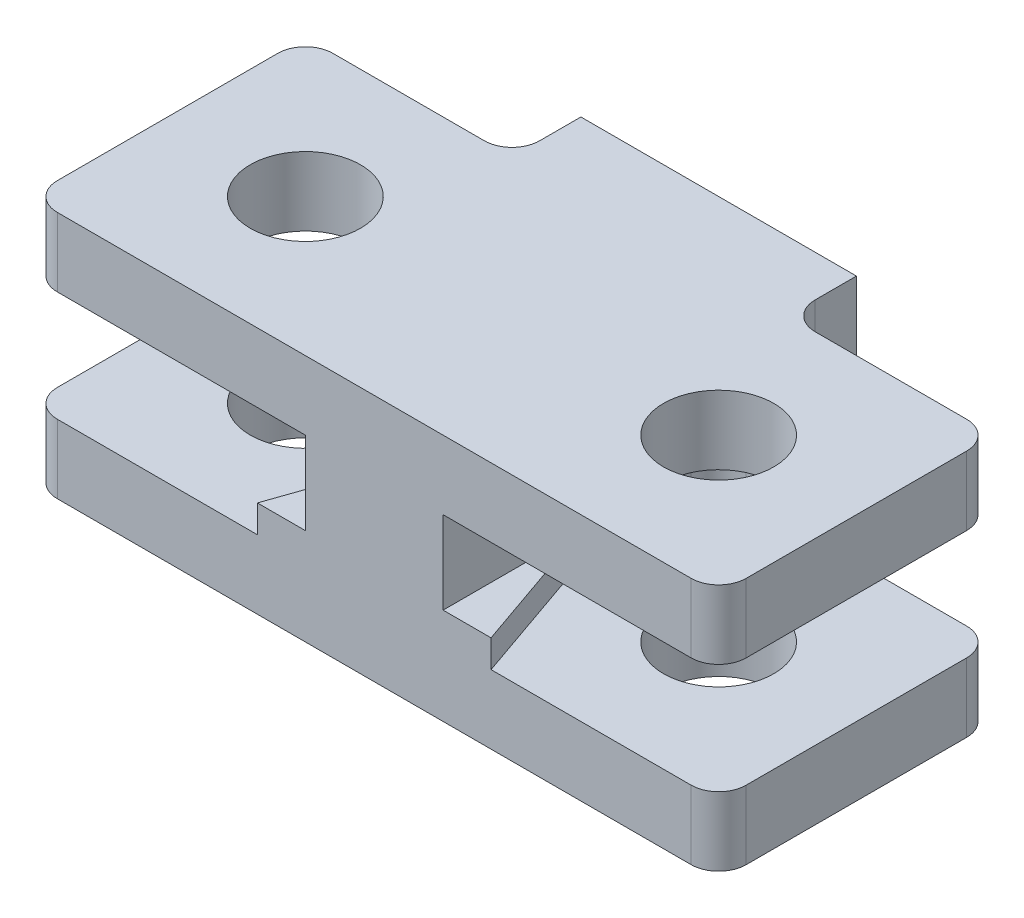
SolidWorks part; units mm, degrees
ref_plane "Front Plane" through (0, 0, 0) normal (0, 0, 1) x (1, 0, 0)
ref_plane "Top Plane" through (0, 0, 0) normal (0, 1, 0) x (1, 0, 0)
ref_plane "Right Plane" through (0, 0, 0) normal (1, 0, 0) x (0, 0, -1)
sketch "Sketch1" plane through (0, 0, 0) normal (0, 1, 0) x (1, 0, 0)
  line L0 (-25, 10) -> (25, -10) construction
  line L1 (-25, -10) -> (25, -10)
  line L2 (-25, -10) -> (-25, 10)
  line L3 (-25, 10) -> (25, 10)
  line L4 (25, -10) -> (25, 10)
  line L5 (-25, -10) -> (25, 10) construction
  point P5 (0, 0)
  dimension "D1" = 50
  dimension "D2" = 20
extrude "Boss-Extrude1" add sketch "Sketch1" along normal blind 5
sketch "Sketch2" plane through (0, 5, 0) normal (0, 1, 0) x (1, 0, 0)
  line L0 (0, -10) -> (0, 10) construction
  line L1 (-25, -10) -> (25, -10) construction
  line L2 (25, 10) -> (-25, 10) construction
  line L3 (-5, 0) -> (-8.48, -10)
  line L4 (-5, 10) -> (5, 10) construction
  line L5 (-5, 10) -> (-5, -10) construction
  line L6 (-5, -10) -> (5, -10) construction
  line L7 (5, 10) -> (5, -10) construction
  line L8 (-5, 10) -> (5, -10) construction
  line L9 (-5, -10) -> (5, 10) construction
  line L10 (-5, 0) -> (-5, -10)
  line L11 (-5, -10) -> (-8.48, -10)
  line L12 (5, 0) -> (5, -10)
  line L13 (5, 0) -> (8.48, -10)
  line L14 (5, -10) -> (8.48, -10)
  circle A0 centre (-15, 0) radius 4
  circle A1 centre (15, 0) radius 4
  point P11 (0, 0)
  line M4 (-25, -10) -> (25, -10)
  dimension "D1" = 8
  dimension "D2" = 15
  dimension "D3" = 10
  dimension "D4" = 10
  dimension "D5" = 8.48
extrude "Cut-Extrude1" cut sketch "Sketch2" against normal blind 5 contours A0 | A1 region at (-15, 5, 0) region at (15, 5, 0)
sketch "Sketch3" plane through (0, 5, 0) normal (0, 1, 0) x (1, 0, 0)
  line L0 (-25, 10) -> (25, -10) construction
  line L1 (0, 0) -> (25, 10) construction
  line L2 (25, 10) -> (-25, 10) construction
  line L3 (-5, -10) -> (5, -10)
  line L4 (-5, -10) -> (-5, 10)
  line L5 (-5, 10) -> (5, 10)
  line L6 (5, -10) -> (5, 10)
  line L7 (-5, -10) -> (5, 10) construction
  line L8 (-5, 10) -> (5, -10) construction
  line L9 (-25, -10) -> (25, -10) construction
  line L10 (5, 0) -> (8.48, -10) construction
  line L11 (8.48, -10) -> (5, -10) construction
  line L13 (0, 10) -> (0, -10) construction
  point P9 (0, 0)
  point P10 (0, 0)
  point P16 (10, -10)
  point P18 (8.48, -10)
  dimension "D1" = 10
  dimension "D2" = 8.48
extrude "Boss-Extrude2" add sketch "Sketch3" along normal blind 8
ref_plane "Plane1" through (0, 9, 0) normal (0, 1, 0) x (1, 0, 0)
mirror "Mirror1" about plane through (0, 9, 0) normal (0, 1, 0) of "Cut-Extrude1", "Boss-Extrude1"
fillet "Fillet1" radius 2 8 edges at (25, 2.5, -10) (25, 15.5, -10) (25, 15.5, 10) (25, 2.5, 10) (-25, 15.5, -10) (-25, 15.5, 10) (-25, 2.5, 10) (-25, 2.5, -10)
sketch "Sketch5" plane through (0, 0, -10) normal (0, 0, 1) x (1, 0, 0)
  line L0 (-10, 0) -> (-10, 18)
  line L1 (-23, 0) -> (23, 0) construction
  line L2 (-23, 18) -> (23, 18) construction
  line L3 (-10, 18) -> (10, 18)
  line L4 (10, 18) -> (10, 0)
  line L5 (10, 0) -> (-10, 0)
  point P8 (0, 0)
  dimension "D1" = 20
  dimension "D2" = 18
extrude "Boss-Extrude3" add sketch "Sketch5" against normal blind 5
sketch "Sketch6" plane through (0, 0, -15) normal (0, 0, -1) x (-1, 0, 0)
  line L0 (10, 18) -> (-10, 0) construction
  line L1 (-10, 18) -> (10, 0) construction
  circle A0 centre (0, 9) radius 4
  dimension "D1" = 8
extrude "Cut-Extrude2" cut sketch "Sketch6" against normal blind 5
fillet "Fillet2" radius 2 6 edges at (10, 2.5, -10) (10, 15.5, -10) (5, 9, -10) (-5, 9, -10) (-10, 2.5, -10) (-10, 15.5, -10)
extrude "Boss-Extrude4" add sketch "Sketch2<5>" along normal blind 2 contours L10 L3 M4 | L13 L12 M4 region at (-6.16, 5, 6.6667) region at (6.16, 5, 6.6667)
sketch "Sketch2<5>" plane through (0, 5, 0) normal (0, 1, 0) x (1, 0, 0) same geometry as "Sketch2"
